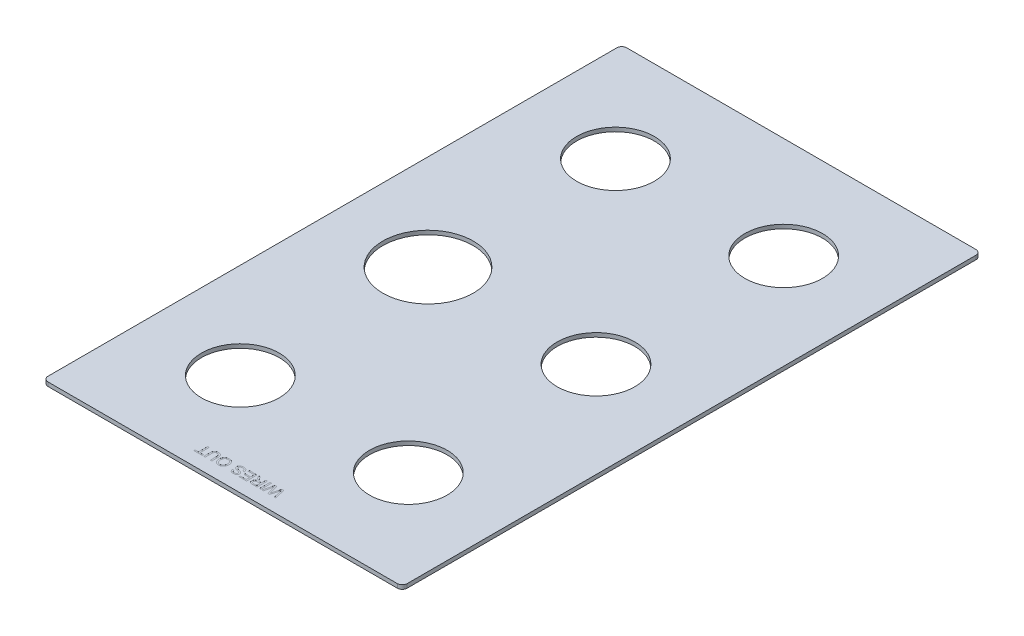
SolidWorks part; units mm, degrees
ref_plane "Front" through (0, 0, 0) normal (0, 0, 1) x (1, 0, 0)
ref_plane "Top" through (0, 0, 0) normal (0, 1, 0) x (1, 0, 0)
ref_plane "Right" through (0, 0, 0) normal (1, 0, 0) x (0, 0, -1)
sketch "Sketch1" plane through (0, 0, 0) normal (0, 1, 0) x (1, 0, 0)
  line L0 (-78.1178, -119.38) -> (-78.2448, -119.38) construction
  line L1 (-111.125, 184.15) -> (111.125, 184.15)
  line L2 (-114.3, 180.975) -> (-114.3, -180.975)
  line L3 (-111.125, -184.15) -> (111.125, -184.15)
  line L4 (114.3, 180.975) -> (114.3, -180.975)
  line L5 (-114.3, 184.15) -> (114.3, -184.15) construction
  line L6 (-114.3, -184.15) -> (114.3, 184.15) construction
  line L7 (-73.1137, 20.0643) -> (-33.9219, -19.9357) construction
  circle A0 centre (53.5178, -119.5086) radius 24.727
  circle A1 centre (53.5178, -0.0643) radius 24.727
  circle A2 centre (-53.5178, -119.38) radius 24.727
  circle A4 centre (-53.5178, 119.38) radius 24.727
  circle A5 centre (53.5178, 119.38) radius 24.727
  arc A6 (-29.1293, -122.5989) -> (-75.7712, -108.8944) centre (-53.5178, -119.38) ccw construction
  arc A7 (-29.1293, -122.5989) -> (-77.9063, -116.1611) centre (-53.5178, -119.38) ccw construction
  arc A8 (114.3, 180.975) -> (111.125, 184.15) centre (111.125, 180.975) ccw
  arc A9 (-114.3, 180.975) -> (-111.125, 184.15) centre (-111.125, 180.975) cw
  arc A10 (-114.3, -180.975) -> (-111.125, -184.15) centre (-111.125, -180.975) ccw
  arc A11 (111.125, -184.15) -> (114.3, -180.975) centre (111.125, -180.975) ccw
  circle A12 centre (-53.5178, 0.0643) radius 28.7693
  point P0 (0, 0)
  dimension "D3" = 0.127
  dimension "D4" = 3.175
  dimension "D1" = 228.6
  dimension "D2" = 368.3
extrude "Boss-Extrude1" add sketch "Sketch1" along normal blind 2.54
sketch "Sketch2" plane through (0, 2.54, 0) normal (0, 1, 0) x (1, 0, 0)
  line L0 (0, -184.15) -> (0, -168.91) construction
  line L1 (-111.125, -184.15) -> (111.125, -184.15) construction
  line L2 (25.4, -168.91) -> (-25.4, -168.91) construction
  text T0 "WIRES OUT" font "Arial" height in points 26
  point P7 (0, -168.91)
  dimension "D1" = 15.24
  dimension "D2" = 50.8
extrude "Cut-Extrude2" cut sketch "Sketch2" against normal blind 0.0254
